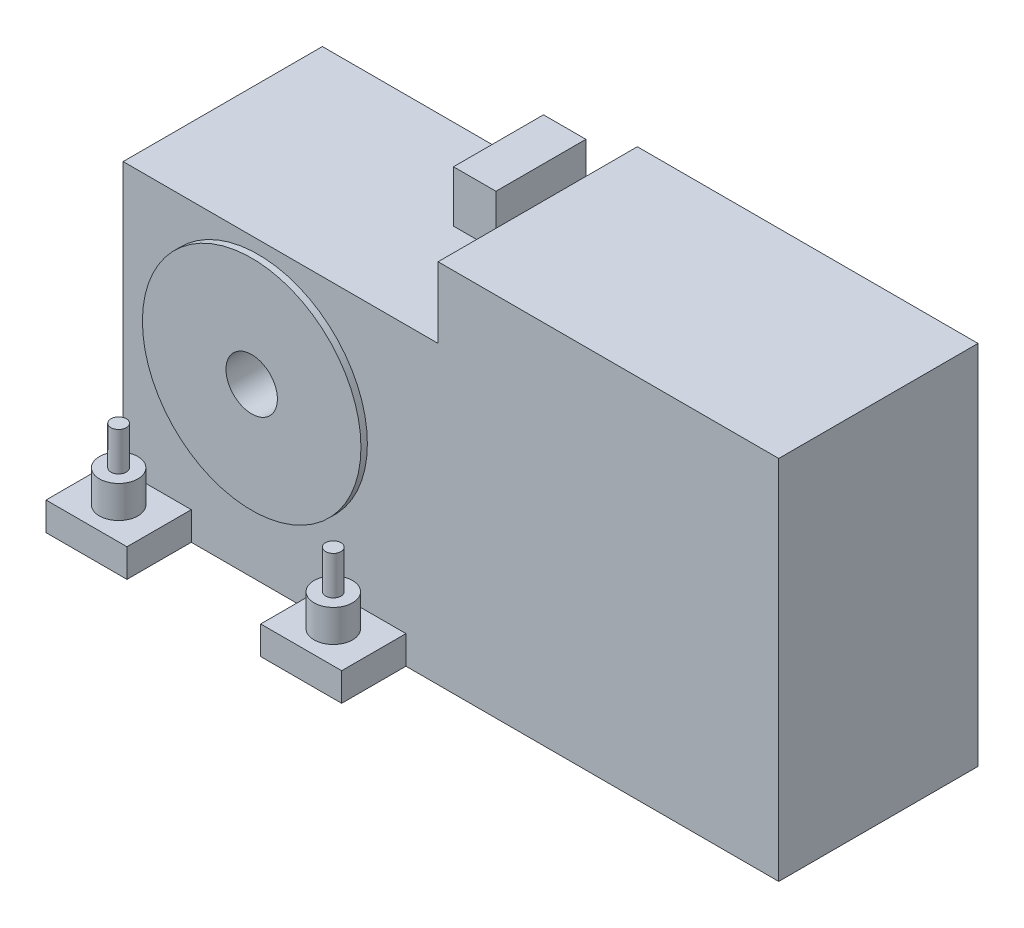
SolidWorks part; units mm, degrees
ref_plane "Front Plane" through (0, 0, 0) normal (0, 0, 1) x (1, 0, 0)
ref_plane "Top Plane" through (0, 0, 0) normal (0, 1, 0) x (1, 0, 0)
ref_plane "Right Plane" through (0, 0, 0) normal (1, 0, 0) x (0, 0, -1)
sketch "Sketch2" plane through (0, 0, 0) normal (0, 0, 1) x (1, 0, 0)
  circle A0 centre (0, 0) radius 85
  circle A1 centre (0, 0) radius 20
  dimension "D1" = 170
  dimension "D2" = 40
extrude "Boss-Extrude1" add sketch "Sketch2" along normal blind 5 contours A0 A1 region at (-82.5958, 0, 0)
sketch "Sketch3" plane through (0, 0, 0) normal (0, 0, -1) x (-1, 0, 0)
  line L1 (-405, 150) -> (-140, 150)
  line L2 (-405, 150) -> (-405, -135)
  line L3 (-405, -135) -> (-140, -135)
  line L4 (-140, 150) -> (-140, -135)
  line L5 (105, 95) -> (-140, 95)
  line L6 (105, 95) -> (105, -135)
  line L7 (105, -135) -> (-140, -135)
  line L8 (-140, 95) -> (-140, -135)
  circle A4 centre (0, 0) radius 85 construction
  circle A5 centre (0, 0) radius 85 construction
  circle M5 centre (0, 0) radius 20
  circle M6 centre (0, 0) radius 85
  dimension "D5" = 55
  dimension "D7" = 10
  dimension "D1" = 230
  dimension "D2" = 55
  dimension "D3" = 265
  dimension "D4" = 20
  dimension "D6" = 510
extrude "Boss-Extrude2" add sketch "Sketch3" along normal blind 155 contours L7 L6 L5 L4 M6 | L4 L1 L2 L3 | M6 M5 region at (272.5, 7.5, 0) region at (17.5, 91.6396, 0) region at (82.5958, 0, 0)
ref_point "Point2"
ref_point "Point4"
ref_axis "x" through (0, 0, 5) along (0, 0, -1)
ref_axis "y" through (0, 0, 5) along (-1, 0, 0)
ref_axis "z" through (0, 0, 5) along (0, 1, 0)
sketch "Sketch4" plane through (0, 0, -155) normal (0, 0, -1) x (-1, 0, 0)
  line L0 (105, 95) -> (-140, 95) construction
  line L1 (-100, 95) -> (-67, 95)
  line L2 (-100, 95) -> (-100, 135)
  line L3 (-100, 135) -> (-67, 135)
  line L4 (-67, 95) -> (-67, 135)
  line L5 (-140, 150) -> (-140, 95) construction
  line L6 (-405, 150) -> (-405, -135) construction
  line L7 (-67, 95) -> (-405, 95)
  line L8 (-67, 95) -> (-67, 135)
  line L9 (-67, 135) -> (-405, 135)
  line L10 (-405, 95) -> (-405, 135)
  line M11 (105, 95) -> (-140, 95)
  dimension "D1" = 33
  dimension "D2" = 40
  dimension "D3" = 40
extrude "Boss-Extrude4" add sketch "Sketch4" against normal blind 70 contours L4 L3 L2 M11 region at (83.5, 115, -155)
sketch "Sketch6" plane through (0, -135, 0) normal (0, -1, 0) x (1, 0, 0)
  line L0 (-105, 0) -> (405, 0) construction
  line L1 (-115, 0) -> (-52, 0)
  line L2 (-115, 0) -> (-115, 50)
  line L3 (-115, 50) -> (-52, 50)
  line L4 (-52, 0) -> (-52, 50)
  line L5 (-52, 50) -> (-115, 0) construction
  line L6 (0, 0) -> (0, 99.6978) construction
  line L7 (115, 50) -> (52, 50)
  line L8 (52, 0) -> (52, 50)
  line L9 (115, 0) -> (52, 0)
  line L10 (115, 0) -> (115, 50)
  circle A0 centre (-83.5, 25) radius 6
  circle A1 centre (-83.5, 25) radius 15
  circle A2 centre (83.5, 25) radius 6
  circle A3 centre (83.5, 25) radius 15
  line M8 (405, 0) -> (-105, 0)
  dimension "D2" = 12
  dimension "D3" = 30
  dimension "D5" = 197
  dimension "D1" = 63
  dimension "D4" = 50
extrude "Boss-Extrude6" add sketch "Sketch6" against normal blind 22 contours L4 L3 L2 L1 A1 M8 | L10 L7 L8 A3 M8 region at (-114.1957, -135, 25) region at (52.8043, -135, 25)
extrude "Boss-Extrude7" add sketch "Sketch6<3>" against normal blind 47 contours A1 A0 | A3 A2 region at (-98.0757, -135, 25) region at (68.9243, -135, 25)
sketch "Sketch6<3>" plane through (0, -135, 0) normal (0, -1, 0) x (1, 0, 0) same geometry as "Sketch6"
extrude "Boss-Extrude8" add sketch "Sketch6<4>" against normal blind 77 contours A0 | A2 region at (-83.5, -135, 25) region at (83.5, -135, 25)
sketch "Sketch6<4>" plane through (0, -135, 0) normal (0, -1, 0) x (1, 0, 0) same geometry as "Sketch6"
